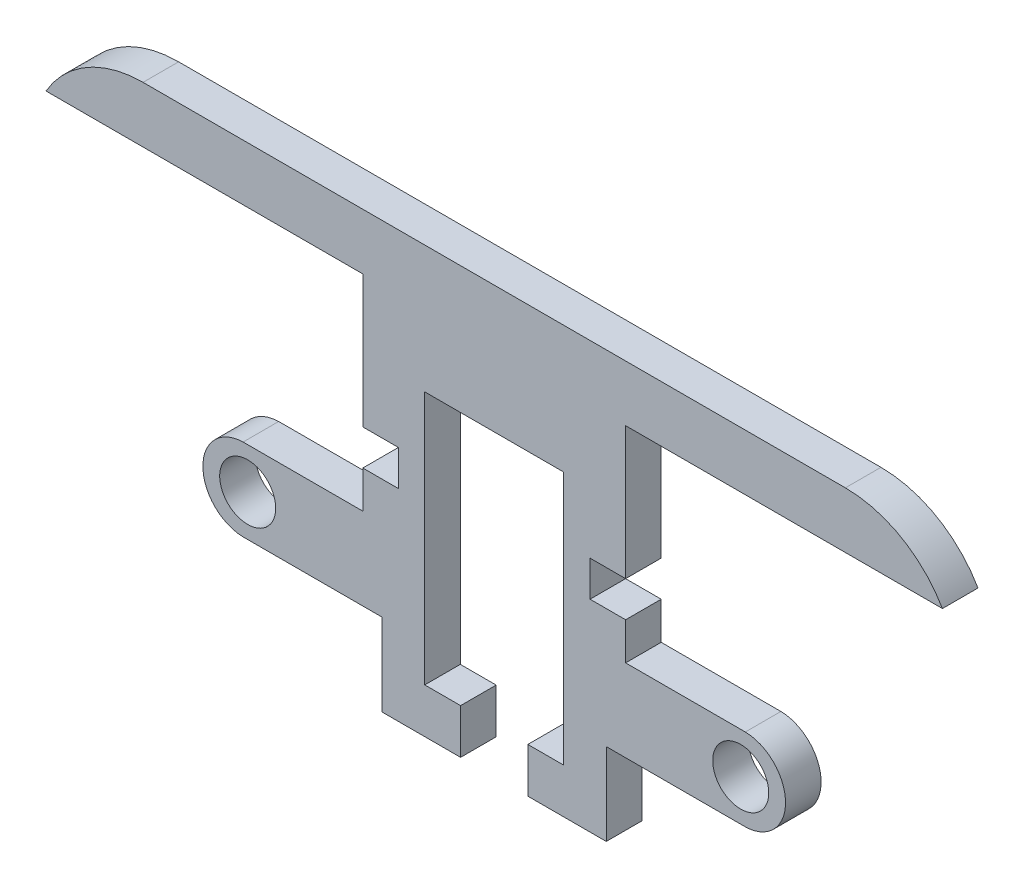
SolidWorks part; units mm, degrees
ref_plane "Front Plane" through (0, 0, 0) normal (0, 0, 1) x (1, 0, 0)
ref_plane "Top Plane" through (0, 0, 0) normal (0, 1, 0) x (1, 0, 0)
ref_plane "Right Plane" through (0, 0, 0) normal (1, 0, 0) x (0, 0, -1)
sketch "Sketch1" plane through (0, 0, 0) normal (0, 0, 1) x (1, 0, 0)
  line L0 (0, 41.2415) -> (0, -44.2517) construction
  line L1 (-63.3907, 0) -> (63.762, 0) construction
  line L2 (-9.56, -41.4376) -> (9.56, -41.4376)
  line L3 (21.91, -41.4376) -> (21.91, -32.4376)
  line L4 (21.91, -9.4376) -> (40, -9.4376)
  line L5 (40, -9.4376) -> (40, 30.5624)
  line L6 (40, 30.5624) -> (10, 30.5624)
  line L7 (10, 30.5624) -> (10, 45.5624)
  line L8 (12.735, -31.7231) -> (12.735, -41.4376) construction
  line L9 (-10, 59.5624) -> (-8.5528, 59.5624)
  line L10 (10, 59.5624) -> (8.5528, 59.5624)
  line L11 (11.7278, 62.7374) -> (11.7278, 74.5624)
  line L12 (11.7278, 74.5624) -> (40, 74.5624)
  line L13 (40, 74.5624) -> (40, 79.5624)
  line L14 (-40, 79.5624) -> (40, 79.5624)
  line L15 (0, 41.2415) -> (0, 85.4214) construction
  line L16 (22, 52.5624) -> (-14.5, 52.5624) construction
  line L17 (8.5528, 59.5624) -> (8.5528, 62.7374)
  line L18 (8.5528, 62.7374) -> (11.7278, 62.7374)
  line L19 (15.91, -41.4376) -> (21.91, -41.4376)
  line L20 (12.735, -41.4376) -> (12.735, -38.2626)
  line L21 (22, 50.0624) -> (22, 45.5624) construction
  line L22 (-10, 45.5624) -> (-10, 48.8958)
  line L23 (12.735, -38.2626) -> (9.56, -38.2626)
  line L24 (21.91, -20.4376) -> (21.91, -9.4376)
  line L25 (10, 59.5624) -> (-10, 59.5624) construction
  line L26 (21.91, -20.4376) -> (18.735, -20.4376)
  line L27 (18.735, -20.4376) -> (18.735, -32.4376)
  line L28 (18.735, -32.4376) -> (21.91, -32.4376)
  line L29 (9.56, -38.2626) -> (9.56, -41.4376)
  line L30 (12.735, -41.4376) -> (15.91, -41.4376)
  line L31 (21.91, -9.4376) -> (21.91, 3.0624) construction
  line L32 (-11.7278, 56.229) -> (-22.4103, 56.229)
  line L33 (-12.735, -31.7231) -> (-12.735, -41.4376) construction
  line L34 (11.7278, 62.7374) -> (11.7278, 56.229) construction
  line L35 (-19.5, 52.5624) -> (-22, 52.5624) construction
  line L36 (-12.735, -41.4376) -> (-15.91, -41.4376)
  line L37 (-9.56, -38.2626) -> (-9.56, -41.4376)
  line L38 (-18.735, -32.4376) -> (-21.91, -32.4376)
  line L39 (-18.735, -20.4376) -> (-18.735, -32.4376)
  line L40 (-21.91, -20.4376) -> (-18.735, -20.4376)
  line L41 (-21.91, -20.4376) -> (-21.91, -9.4376)
  line L42 (-12.735, -38.2626) -> (-9.56, -38.2626)
  line L43 (10, 59.5624) -> (11.7278, 59.5624)
  line L44 (11.7278, 59.5624) -> (11.7278, 56.229)
  line L45 (-12.735, -41.4376) -> (-12.735, -38.2626)
  line L46 (-15.91, -41.4376) -> (-21.91, -41.4376)
  line L47 (-8.5528, 62.7374) -> (-11.7278, 62.7374)
  line L48 (-8.5528, 59.5624) -> (-8.5528, 62.7374)
  line L49 (-40, 74.5624) -> (-40, 79.5624)
  line L50 (-11.7278, 74.5624) -> (-40, 74.5624)
  line L51 (-11.7278, 62.7374) -> (-11.7278, 74.5624)
  line L52 (-10, 59.5624) -> (-8.5528, 59.5624)
  line L53 (-11.7278, 59.5624) -> (-11.7278, 56.229)
  line L54 (-10, 30.5624) -> (-10, 45.5624)
  line L55 (-40, 30.5624) -> (-10, 30.5624)
  line L56 (-40, -9.4376) -> (-40, 30.5624)
  line L57 (-21.91, -9.4376) -> (-40, -9.4376)
  line L58 (-21.91, -41.4376) -> (-21.91, -32.4376)
  line L59 (10, 45.5624) -> (10, 56.229) construction
  line L60 (22, 45.5624) -> (31.5207, 45.5624) construction
  line L61 (-10, 48.8958) -> (-22.4103, 48.8958)
  line L62 (22, 55.0624) -> (22, 59.5624) construction
  line L63 (-10, 59.5624) -> (-11.7278, 59.5624)
  line L64 (18.8205, 56.229) -> (11.7278, 56.229) construction
  line L65 (18.8205, 48.8958) -> (10, 48.8958) construction
  line L66 (22, 47.9767) -> (26, 47.9767) construction
  line L67 (18.8205, 48.8958) -> (22.4103, 48.8958) construction
  line L68 (26, 47.9767) -> (26, 56.3586) construction
  line L69 (18.8205, 56.229) -> (26, 56.229) construction
  line L70 (21.91, 3.0624) -> (-21.91, 3.0624) construction
  line L71 (11.7278, 56.229) -> (22.4103, 56.229)
  line L72 (10, 45.5624) -> (10, 48.8958)
  line L73 (10, 48.8958) -> (22.4103, 48.8958)
  line L74 (-21.91, 3.0624) -> (-21.91, -9.4376) construction
  line L76 (-4, 1.5624) -> (4, 1.5624)
  line L77 (-5, 2.5624) -> (-5, 3.5624)
  line L78 (-4, 4.5624) -> (4, 4.5624)
  line L79 (5, 2.5624) -> (5, 3.5624)
  line L80 (-5, 1.5624) -> (5, 4.5624) construction
  line L81 (-5, 4.5624) -> (5, 1.5624) construction
  circle A0 centre (-22, 52.5624) radius 2.5
  arc A1 (4, 4.5624) -> (5, 3.5624) centre (4, 3.5624) cw
  arc A2 (22.4103, 56.229) -> (22.4103, 48.8958) centre (22.3326, 52.5624) cw
  circle A3 centre (22, 52.5624) radius 2.5
  arc A4 (-22.4103, 56.229) -> (-22.4103, 48.8958) centre (-22.3326, 52.5624) ccw
  arc A5 (5, 2.5624) -> (4, 1.5624) centre (4, 2.5624) cw
  arc A6 (-4, 1.5624) -> (-5, 2.5624) centre (-4, 2.5624) cw
  arc A7 (-5, 3.5624) -> (-4, 4.5624) centre (-4, 3.5624) cw
  spline S1 degree 1 poles (0, 79.5624) (40, 79.5624) knots 0 0 1 1
  spline S2 degree 1 poles (0, 79.5624) (-40, 79.5624) knots 0 0 1 1
  point P23 (10, 38.0624)
  point P26 (0, 3.0624)
  point P45 (0, 59.5624)
  point P46 (0, 52.5624)
  point P71 (0, 79.5624)
  point P77 (0, -41.4376)
  dimension "D12" = 10
  dimension "D13" = 1
  dimension "D6" = 40
  dimension "D1" = 21.91
  dimension "D2" = 32
  dimension "D3" = 40
  dimension "D4" = 18.09
  dimension "D5" = 15
  dimension "D7" = 12.5
  dimension "D8" = 5
  dimension "D9" = 9.175
  dimension "D10" = 3
  dimension "D11" = 10
  dimension "D14" = 21.5207
  dimension "D15" = 3.175
  dimension "D16" = 9
  dimension "D17" = 12
  dimension "D18" = 3.175
  dimension "D19" = 3.175
  dimension "D20" = 3.175
  dimension "D21" = 3.175
  dimension "D22" = 4
extrude "Boss-Extrude1" add sketch "Sketch1" along normal blind 3.175 contours L54 L55 L56 L57 L41 L40 L39 L38 L58 L46 L36 L45 L42 L37 L2 L29 L23 L20 L30 L19 L3 L28 L27 L26 L24 L4 L5 L6 L7 L32 L10 L17 L18 L11 L12 L13 L14 L49 L50 region at (0, 15.1263, 0)
fillet "Fillet1" radius 10 2 edges at (-40, 79.5624, 1.5875) (40, 79.5624, 1.5875)
sketch "Sketch2" plane through (0, 0, 3.175) normal (0, 0, 1) x (1, 0, 0)
  line L0 (-21.91, -36.6376) -> (21.91, -36.6376) construction
  line L1 (-21.91, -41.4376) -> (-21.91, -32.4376) construction
  line L2 (21.91, -41.4376) -> (21.91, -32.4376) construction
  line L3 (-12.735, -41.4376) -> (-21.91, -41.4376) construction
  line L4 (-17.11, -41.4376) -> (-17.11, -8.6603) construction
  line L6 (-17.11, -36.6376) -> (-8.11, -36.6376)
  line L7 (-17.11, -36.6376) -> (-17.11, -15.6376)
  line L8 (-17.11, -15.6376) -> (-8.11, -15.6376)
  line L9 (-8.11, -36.6376) -> (-8.11, -15.6376)
  dimension "D1" = 4.8
  dimension "D2" = 4.8
  dimension "D3" = 21
  dimension "D4" = 9
extrude "Cut-Extrude1" cut sketch "Sketch2" against normal through all
fillet "Fillet2" radius 10 4 edges at (-40, -9.4376, 1.5875) (40, -9.4376, 1.5875) (40, 30.5624, 1.5875) (-40, 30.5624, 1.5875)
sketch "Sketch4" plane through (0, -41.4376, 0) normal (0, -1, 0) x (1, 0, 0)
  line L1 (-45.1719, -14.5797) -> (45.1719, -14.5797)
  line L2 (-45.1719, -14.5797) -> (-45.1719, 14.5797)
  line L3 (-45.1719, 14.5797) -> (45.1719, 14.5797)
  line L4 (45.1719, -14.5797) -> (45.1719, 14.5797)
  line L5 (-45.1719, -14.5797) -> (45.1719, 14.5797) construction
  line L6 (-45.1719, 14.5797) -> (45.1719, -14.5797) construction
  point P0 (0, 0)
extrude "Cut-Extrude3" cut sketch "Sketch4" against normal blind 83
sketch "Sketch5" plane through (0, 0, 3.175) normal (0, 0, 1) x (1, 0, 0)
  line L0 (6.2, 68.2124) -> (6.2, 45.5624) construction
  line L1 (-11.7278, 62.7374) -> (-11.7278, 74.5624) construction
  line L2 (11.7278, 62.7374) -> (11.7278, 74.5624) construction
  line L3 (0, 68.2124) -> (0, 45.5624) construction
  line L4 (-31.3397, 79.5624) -> (31.3397, 79.5624) construction
  line L5 (-6.2, 68.2124) -> (6.2, 68.2124)
  line L6 (-11.7278, 68.2124) -> (11.7278, 68.2124) construction
  line L7 (0, 45.5624) -> (6.2, 45.5624) construction
  line L8 (3, 45.5624) -> (3, 40.5624) construction
  line L9 (6.2, 68.2124) -> (6.2, 45.5624)
  line L10 (6.2, 45.5624) -> (3, 45.5624)
  line L11 (3, 45.5624) -> (3, 40.5624)
  line L12 (10, 40.5624) -> (-10.2276, 40.5624) construction
  line L13 (10, 41.5624) -> (10, 48.8958) construction
  line L14 (-0.1138, 40.5624) -> (3, 40.5624)
  line L15 (-6.2, 68.2124) -> (-6.2, 45.5624)
  line L16 (-6.2, 45.5624) -> (-3, 45.5624)
  line L17 (-3, 45.5624) -> (-3, 40.5624)
  line L18 (0.1138, 40.5624) -> (-3, 40.5624)
  dimension "D1" = 11.35
  dimension "D2" = 6.2
  dimension "D3" = 22.65
  dimension "D4" = 3
  dimension "D5" = 5
extrude "Cut-Extrude4" cut sketch "Sketch5" against normal through all contours L18 L14 L11 L10 L9 L5 L15 L16 L17 region at (0, 55.5532, 3.175)
